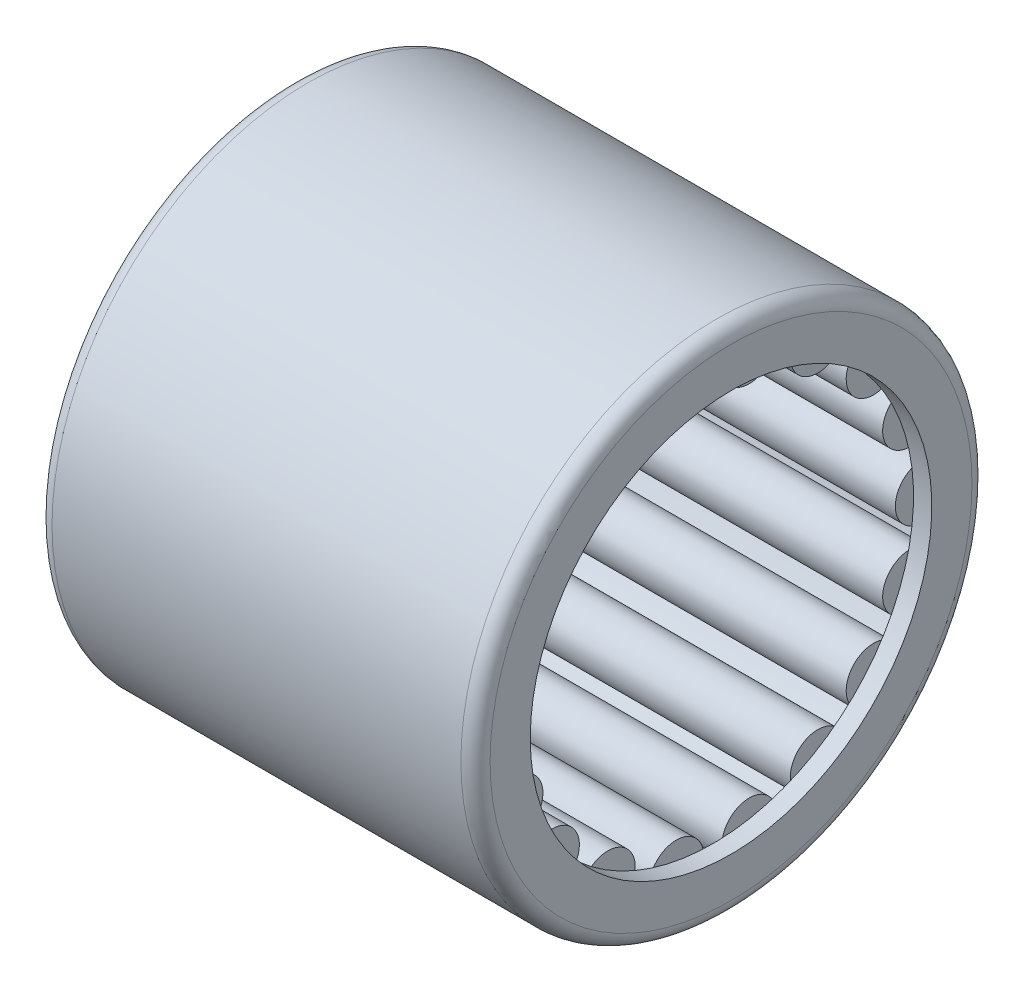
SolidWorks part; units mm, degrees
ref_plane "前视基准面" through (0, 0, 0) normal (0, 0, 1) x (1, 0, 0)
ref_plane "上视基准面" through (0, 0, 0) normal (0, 1, 0) x (1, 0, 0)
ref_plane "右视基准面" through (0, 0, 0) normal (1, 0, 0) x (0, 0, -1)
other "Configuration Table"
sketch "草图2" plane through (0, 0, 0) normal (0, 0, 1) x (1, 0, 0)
sketch "草图3" plane through (0, 0, 0) normal (0, 0, 1) x (1, 0, 0)
  line L0 (-6, 7) -> (-6, 5.5)
  line L1 (-6, 5.5) -> (-5.5, 5.5)
  line L2 (-5.5, 5.5) -> (-5.5, 6.5)
  line L3 (-5.5, 6.5) -> (5.5, 6.5)
  line L4 (5.5, 6.5) -> (5.5, 5.5)
  line L5 (5.5, 5.5) -> (6, 5.5)
  line L6 (6, 5.5) -> (6, 7)
  line L7 (6, 7) -> (-6, 7)
  line L8 (55, 0) -> (-55, 0) construction
  line L10 (0, -55) -> (0, 55) construction
  line L11 (-6.2027, 0) -> (6.3474, 0) construction
  point P10 (-5.5, 6)
  dimension "D1" = 5.5
  dimension "D2" = 5.5
  dimension "D3" = 0.5
  dimension "D4" = 7
  dimension "D5" = 0.5
  dimension "D6" = 0.5
  dimension "D7" = 6
  dimension "D8" = 6
revolve "旋转1" add sketch "草图3" angle 360 about L11
sketch "草图5" plane through (5.5, 0, 0) normal (-1, 0, 0) x (0, 0, 1)
  line L0 (6.6, 0) -> (-6.6, 0) construction
  circle A0 centre (-5.75, 0) radius 0.75
  circle A1 centre (0, 0) radius 6.5 construction
  dimension "D1" = 1.5
extrude "凸台-拉伸3" add sketch "草图5" along normal up to surface (11 mm away) separate body contours A0 up to face at (-5.5, 0, 6.5)
pattern_circular "阵列(圆周)8" count 18 over 360 about axis through (-6.2027, 0, 0) along (-1, 0, 0) of bodies 107
fillet "圆角1" radius 0.4 4 edges at (5.5, 0, 6.5) (-5.5, 0, 6.5) (6, 0, 7) (-6, 0, 7)
